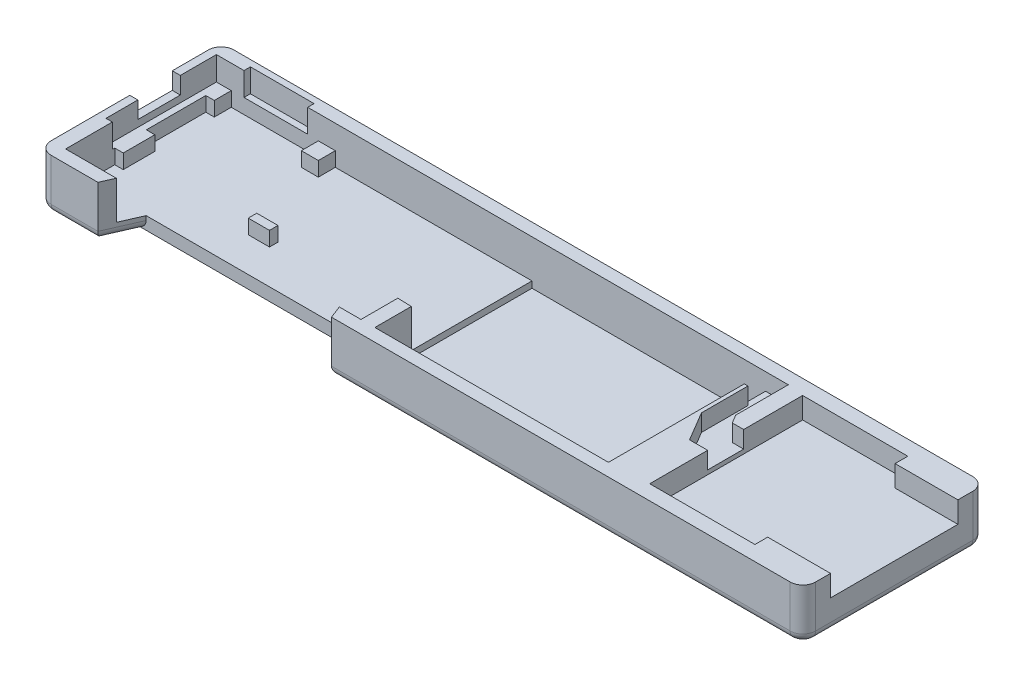
SolidWorks part; units mm, degrees
ref_plane "前视基准面" through (0, 0, 0) normal (0, 0, 1) x (1, 0, 0)
ref_plane "上视基准面" through (0, 0, 0) normal (0, 1, 0) x (1, 0, 0)
ref_plane "右视基准面" through (0, 0, 0) normal (1, 0, 0) x (0, 0, -1)
sketch "草图3" plane through (0, 0, 0) normal (0, 1, 0) x (1, 0, 0)
  line L1 (-39.9314, 29.2531) -> (140.0686, 29.2531)
  line L2 (-39.9314, 29.2531) -> (-39.9314, -13.7469)
  line L3 (-39.9314, -13.7469) -> (140.0686, -13.7469)
  line L4 (140.0686, 29.2531) -> (140.0686, -13.7469)
extrude "凸台-拉伸1" add sketch "草图3" along normal blind 12
sketch "草图4" plane through (0, 0, 0) normal (0, 1, 0) x (1, 0, 0)
  line L0 (-22.4696, -5.8589) -> (26.0023, -5.8589)
  line L1 (-39.9314, -13.7469) -> (140.0686, -13.7469) construction
  line L2 (-25.9314, -13.7469) -> (29.0686, -13.7469)
  line L5 (-25.9314, -13.7469) -> (-22.4696, -5.8589)
  line L6 (29.0686, -13.7469) -> (26.0023, -5.8589)
  point P11 (-22.4696, -5.8589)
  point P12 (26.0023, -5.8589)
extrude "切除-拉伸1" cut sketch "草图4" along normal blind 52
sketch "草图5" plane through (0, 12, 0) normal (0, 1, 0) x (1, 0, 0)
  line L6 (140.0686, -13.7469) -> (140.0686, 29.2531) construction
  line L7 (140.0686, 7.7531) -> (140.0686, 22.7531)
  line L8 (140.0686, 7.7531) -> (140.0686, -7.2469)
  line L9 (140.0686, 22.7531) -> (125.2765, 22.7531)
  line L10 (125.2765, 22.7531) -> (125.2765, -7.2469)
  line L11 (125.2765, -7.2469) -> (140.0686, -7.2469)
  point P0 (140.0686, 7.7531)
extrude "切除-拉伸2" cut sketch "草图5" against normal blind 5
sketch "草图7" plane through (0, 12, 0) normal (0, 1, 0) x (1, 0, 0)
  line L0 (125.2765, 22.7531) -> (125.2765, -7.2469) construction
  line L1 (125.2765, 7.7531) -> (125.2765, 25.7531)
  line L2 (125.2765, 7.7531) -> (125.2765, -10.2469)
  line L3 (125.2765, -10.2469) -> (100.5008, -10.2469)
  line L4 (100.5008, -10.2469) -> (100.5008, 25.7531)
  line L5 (100.5008, 25.7531) -> (125.2765, 25.7531)
  point P0 (125.2765, 7.7531)
extrude "切除-拉伸3" cut sketch "草图7" against normal blind 5
sketch "草图8" plane through (0, 12, 0) normal (0, 1, 0) x (1, 0, 0)
  line L1 (36.2763, 26.2531) -> (91.2763, 26.2531)
  line L2 (36.2763, 26.2531) -> (36.2763, -10.7469)
  line L3 (36.2763, -10.7469) -> (91.2763, -10.7469)
  line L4 (91.2763, 26.2531) -> (91.2763, -10.7469)
  line L6 (140.0686, 29.2531) -> (-39.9314, 29.2531) construction
  line L7 (29.0686, -13.7469) -> (140.0686, -13.7469) construction
  dimension "D1" = 3
  dimension "D2" = 3
extrude "切除-拉伸4" cut sketch "草图8" against normal blind 10.5
sketch "草图9" plane through (0, 12, 0) normal (0, 1, 0) x (1, 0, 0)
  line L0 (91.2763, -10.7469) -> (91.2763, 26.2531) construction
  line L1 (91.2763, 26.2531) -> (96.6358, 26.2531)
  line L2 (91.2763, 26.2531) -> (91.2763, 21.2551)
  line L4 (96.6358, 26.2531) -> (96.6358, 22.1306)
  line L5 (100.5008, 25.7531) -> (100.5008, -10.2469) construction
  line L7 (92.1327, 21.2551) -> (92.1327, 10.3104)
  line L12 (96.2367, 3.394) -> (100.5008, 3.394)
  line L13 (100.5008, 11.8772) -> (100.5008, 3.394)
  line L14 (92.1327, 10.3104) -> (96.2367, 3.394)
  line L15 (96.6358, 13.8621) -> (97.8136, 11.8772)
  line L17 (97.8136, 11.8772) -> (100.5008, 11.8772)
  line L19 (96.6358, 13.8621) -> (96.6358, 22.1306)
  line L20 (92.1327, 21.2551) -> (91.2763, 21.2551)
extrude "切除-拉伸5" cut sketch "草图9" against normal blind 4
sketch "草图10" plane through (0, 12, 0) normal (0, 1, 0) x (1, 0, 0)
  line L4 (-29.1302, -10.7469) -> (32.9986, -10.7469)
  line L5 (-29.1302, -10.7469) -> (-29.1302, -2.0631)
  line L6 (-29.1302, -2.0631) -> (32.9986, -2.0631)
  line L7 (32.9986, -10.7469) -> (32.9986, -2.0631)
extrude "切除-拉伸6" cut sketch "草图10" against normal blind 8
sketch "草图11" plane through (0, 12, 0) normal (0, 1, 0) x (1, 0, 0)
  line L0 (32.9986, -10.7469) -> (-36.5397, -10.7469)
  line L1 (36.2763, 26.2531) -> (36.2763, -10.7469) construction
  line L5 (-36.5397, 26.2531) -> (-36.5397, -10.7469)
  line L9 (36.2763, 26.2531) -> (36.2763, -2.1672)
  line L10 (-36.5397, 26.2531) -> (36.2763, 26.2531)
  line L11 (32.9986, -10.7469) -> (32.9986, -2.0631)
  line L12 (32.9986, -10.7469) -> (32.9986, -2.0631) construction
  line L13 (32.9986, -2.0631) -> (36.2763, -2.1672)
extrude "切除-拉伸8" cut sketch "草图11" against normal blind 9
fillet "圆角2" radius 2 7 edges at (140.0686, 0, -7.7531) (84.5686, 0, 13.7469) (27.5354, 0, 9.8029) (-24.2005, 0, 9.8029) (-32.9314, 0, 13.7469) (-39.9314, 0, -7.7531) (50.0686, 0, -29.2531)
fillet "圆角3" radius 3 8 edges at (-39.3456, 0.5858, -28.6673) (-39.3456, 0.5858, 13.1611) (139.4828, 0.5858, 13.1611) (139.4828, 0.5858, -28.6673) (140.0686, 7, -29.2531) (140.0686, 7, 13.7469) (-39.9314, 7, 13.7469) (-39.9314, 7, -29.2531)
sketch "草图12" plane through (-36.5397, 0, 0) normal (1, 0, 0) x (0, 0, -1)
  line L5 (7.7531, 12) -> (17.7531, 12)
  line L6 (7.7531, 12) -> (7.7531, 8)
  line L7 (7.7531, 8) -> (17.7531, 8)
  line L8 (17.7531, 12) -> (17.7531, 8)
  line L9 (26.2531, 3) -> (26.2531, 12) construction
  dimension "D1" = 10
  dimension "D2" = 8.5
  dimension "D3" = 4
extrude "切除-拉伸9" cut sketch "草图12" against normal blind 10
sketch "草图13" plane through (0, 3, 0) normal (0, 1, 0) x (1, 0, 0)
  line L0 (-36.5397, 26.2531) -> (-36.5397, -10.7469) construction
  line L1 (-36.5397, 22.2531) -> (-34.5397, 22.2531)
  line L2 (-36.5397, 22.2531) -> (-36.5397, 26.2531)
  line L3 (-36.5397, 26.2531) -> (-34.5397, 26.2531)
  line L4 (-34.5397, 22.2531) -> (-34.5397, 26.2531)
  line L5 (36.2763, 26.2531) -> (-36.5397, 26.2531) construction
  line L7 (-36.5397, 8.2531) -> (-34.5397, 8.2531)
  line L8 (-36.5397, 8.2531) -> (-36.5397, 0.8178)
  line L9 (-36.5397, 0.8178) -> (-34.5397, 0.8178)
  line L10 (-34.5397, 8.2531) -> (-34.5397, 0.8178)
  line L11 (-14.0397, 26.2531) -> (-10.0397, 26.2531)
  line L12 (-14.0397, 26.2531) -> (-14.0397, 22.2531)
  line L13 (-14.0397, 22.2531) -> (-10.0397, 22.2531)
  line L14 (-10.0397, 26.2531) -> (-10.0397, 22.2531)
  line L15 (-36.5397, 7.7531) -> (-36.5397, -10.7469) construction
  line L16 (-6.5397, 4.2531) -> (-1.5397, 4.2531)
  line L17 (-6.5397, 4.2531) -> (-6.5397, 2.2531)
  line L18 (-6.5397, 2.2531) -> (-1.5397, 2.2531)
  line L19 (-1.5397, 4.2531) -> (-1.5397, 2.2531)
  line L20 (96.6358, 26.2531) -> (-36.5397, 26.2531) construction
  point P16 (-14.0397, 24.2531)
  dimension "D1" = 14
  dimension "D2" = 4
  dimension "D3" = 2
  dimension "D4" = 2
  dimension "D5" = 22.5
  dimension "D6" = 4
  dimension "D7" = 4
  dimension "D8" = 30
  dimension "D9" = 5
  dimension "D10" = 2
  dimension "D11" = 22
extrude "凸台-拉伸2" add sketch "草图13" along normal blind 3.4
sketch "草图14" plane through (0, 12, 0) normal (0, 1, 0) x (1, 0, 0)
  line L0 (96.6358, 26.2531) -> (-36.5397, 26.2531) construction
  line L1 (-16.5397, 26.2531) -> (-31.5397, 26.2531)
  line L2 (-16.5397, 26.2531) -> (-16.5397, 27.7531)
  line L3 (-16.5397, 27.7531) -> (-31.5397, 27.7531)
  line L4 (-31.5397, 26.2531) -> (-31.5397, 27.7531)
  line L5 (91.2763, 26.2531) -> (36.2763, 26.2531) construction
  line L6 (-36.5397, 26.2531) -> (-36.5397, 17.7531) construction
  point P8 (-31.5397, 27.0031)
  dimension "D1" = 15
  dimension "D2" = 5
  dimension "D3" = 1.5
extrude "切除-拉伸10" cut sketch "草图14" against normal blind 5.5
sketch "草图15" plane through (0, 12, 0) normal (0, 1, 0) x (1, 0, 0)
  line L6 (-36.5397, 0.2531) -> (-38.0397, 0.2531)
  line L7 (-36.5397, 0.2531) -> (-36.5397, 26.2531)
  line L8 (-36.5397, 26.2531) -> (-38.0397, 26.2531)
  line L9 (-38.0397, 0.2531) -> (-38.0397, 26.2531)
  dimension "D1" = 1.5
  dimension "D2" = 26
extrude "切除-拉伸11" cut sketch "草图15" against normal blind 5.6
equation "\"3。4.00mm\"=5"
